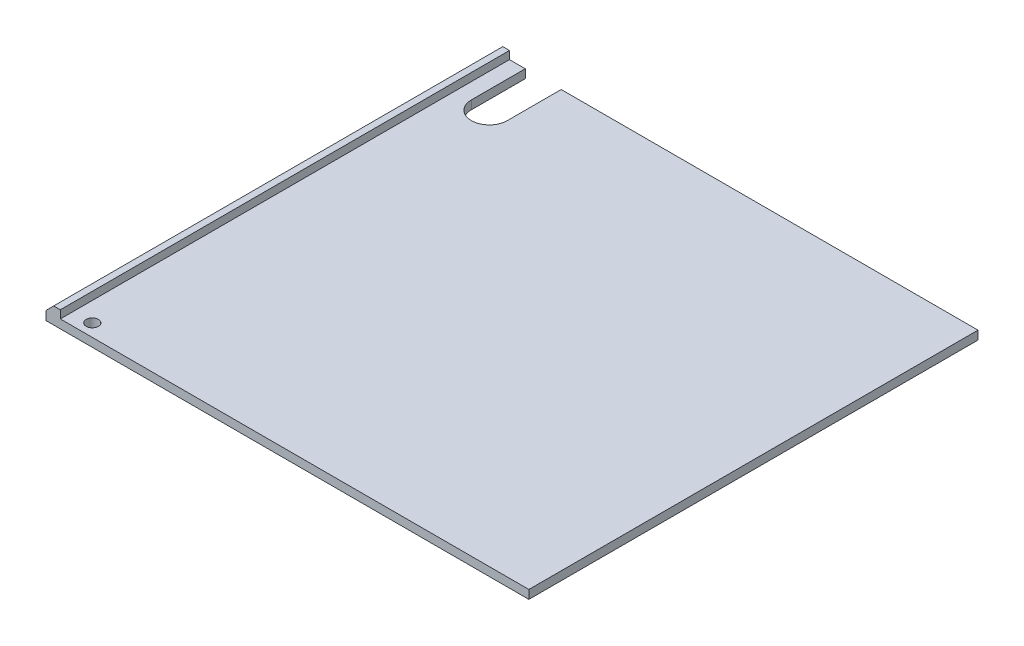
SolidWorks part; units mm, degrees
material "ABS"
ref_plane "Front Plane" through (0, 0, 0) normal (0, 0, 1) x (1, 0, 0)
ref_plane "Top Plane" through (0, 0, 0) normal (0, 1, 0) x (1, 0, 0)
ref_plane "Right Plane" through (0, 0, 0) normal (1, 0, 0) x (0, 0, -1)
ref_axis "Axis1" through (0, 0, 55) along (0, 0, -1)
sketch "Sketch1" plane through (0, 0, 0) normal (0, 1, 0) x (1, 0, 0)
  line L1 (-64.25, 62.5) -> (64.25, 62.5)
  line L2 (-64.25, 62.5) -> (-64.25, -62.5)
  line L3 (-64.25, -62.5) -> (64.25, -62.5)
  line L4 (64.25, 62.5) -> (64.25, -62.5)
  line L5 (-64.25, 62.5) -> (64.25, -62.5) construction
  line L6 (-64.25, -62.5) -> (64.25, 62.5) construction
  point P0 (0, 0)
  dimension "D1" = 128.5
  dimension "D2" = 125
extrude "Boss-Extrude1" add sketch "Sketch1" along normal blind 2.4
sketch "4040-extrusion" plane through (0, 0, 62.5) normal (0, 0, 1) x (1, 0, 0)
  line L0 (-64.25, 0) -> (-64.25, 9.5) construction
  line L1 (-64.25, 9.5) -> (-64.25, 4.3) construction
  line L2 (-64.25, 4.3) -> (-66.05, 2.5) construction
  line L3 (-66.05, 2.5) -> (-66.05, 4.71) construction
  line L4 (-66.05, 4.71) -> (-68.05, 4.71) construction
  line L5 (-68.05, 4.71) -> (-70.2381, 2.5) construction
  line L6 (-70.2381, 2.5) -> (-70.2381, 0) construction
  dimension "D1" = 9.5
  dimension "D2" = 5.2
  dimension "D3" = 7
  dimension "D4" = 1.8
  dimension "D5" = 2.21
  dimension "D6" = 2
  dimension "D7" = 3.11
sketch "Sketch3" plane through (0, 0, 62.5) normal (0, 0, 1) x (1, 0, 0)
  line L0 (-64.25, 2.4) -> (-66.05, 2.4)
  line L1 (-66.05, 2.4) -> (-66.05, 4.71) construction
  line L2 (-66.05, 4.71) -> (-68.05, 4.71) construction
  line L3 (-68.05, 4.71) -> (-70.2381, 2.5) construction
  line L4 (-70.2381, 2.5) -> (-70.2381, 0) construction
  line L5 (-70.2381, 0) -> (-70.1381, 0) construction
  line L6 (-64.25, 0) -> (-64.25, 2.4)
  line L7 (-66.15, 2.4) -> (-66.15, 4.61)
  line L8 (-66.15, 4.61) -> (-68.0083, 4.61)
  line L9 (-68.0083, 4.61) -> (-70.1381, 2.4589)
  line L10 (-70.1381, 2.4589) -> (-70.1381, 0)
  line L11 (-66.15, 2.4) -> (-66.05, 2.4)
  line L12 (-70.1381, 0) -> (-64.25, 0)
  dimension "D1" = 0.1
extrude "Boss-Extrude2" add sketch "Sketch3" against normal up to surface (125 mm away) up to face at (0, 1.2, -62.5)
sketch "Sketch5" plane through (0, 2.4, 0) normal (0, 1, 0) x (1, 0, 0)
  line L0 (-56.75, 62.5) -> (-56.75, 47.5) construction
  line L1 (64.25, 62.5) -> (-66.15, 62.5) construction
  line L2 (-51.75, 62.5) -> (-51.75, 47.5)
  line L3 (-61.75, 62.5) -> (-61.75, 47.5)
  line L5 (-61.75, 62.5) -> (-51.75, 62.5)
  line L6 (-66.15, 62.5) -> (-66.15, -62.5) construction
  arc A0 (-51.75, 62.5) -> (-61.75, 62.5) centre (-56.75, 62.5) ccw
  arc A1 (-61.75, 47.5) -> (-51.75, 47.5) centre (-56.75, 47.5) ccw
  point P4 (-56.75, 55)
  line M5 (64.25, 62.5) -> (-66.15, 62.5)
  dimension "D1" = 5
  dimension "D3" = 15
  dimension "D2" = 9.4
extrude "Cut-Extrude2" cut sketch "Sketch5" against normal through all contours L3 A1 L2 L5 M5 region at (-56.75, 2.4, -53.0036)
sketch "Sketch6" plane through (0, 2.4, 0) normal (0, 1, 0) x (1, 0, 0)
  line L0 (-60.75, -59) -> (-66.15, -59) construction
  line L1 (-66.15, -62.5) -> (64.25, -62.5) construction
  line L3 (-64.25, -62.5) -> (-57.25, -62.5) construction
  line L4 (-64.25, -62.5) -> (-64.25, -55.5) construction
  line L5 (-64.25, -55.5) -> (-57.25, -55.5) construction
  line L6 (-57.25, -62.5) -> (-57.25, -55.5) construction
  line L7 (-64.25, -62.5) -> (-57.25, -55.5) construction
  line L8 (-64.25, -55.5) -> (-57.25, -62.5) construction
  line L9 (-66.15, 62.5) -> (-66.15, -62.5) construction
  circle A0 centre (-60.75, -59) radius 1.7
  point P8 (-60.75, -59)
  dimension "D3" = 3.4
  dimension "D1" = 5.4
  dimension "D2" = 7
extrude "Cut-Extrude3" cut sketch "Sketch6" against normal through all
equation "\"D1@Sketch1\"=125mm+3.5mm"
equation "\"D2@Sketch5\"=5+2+2.3+.1"
